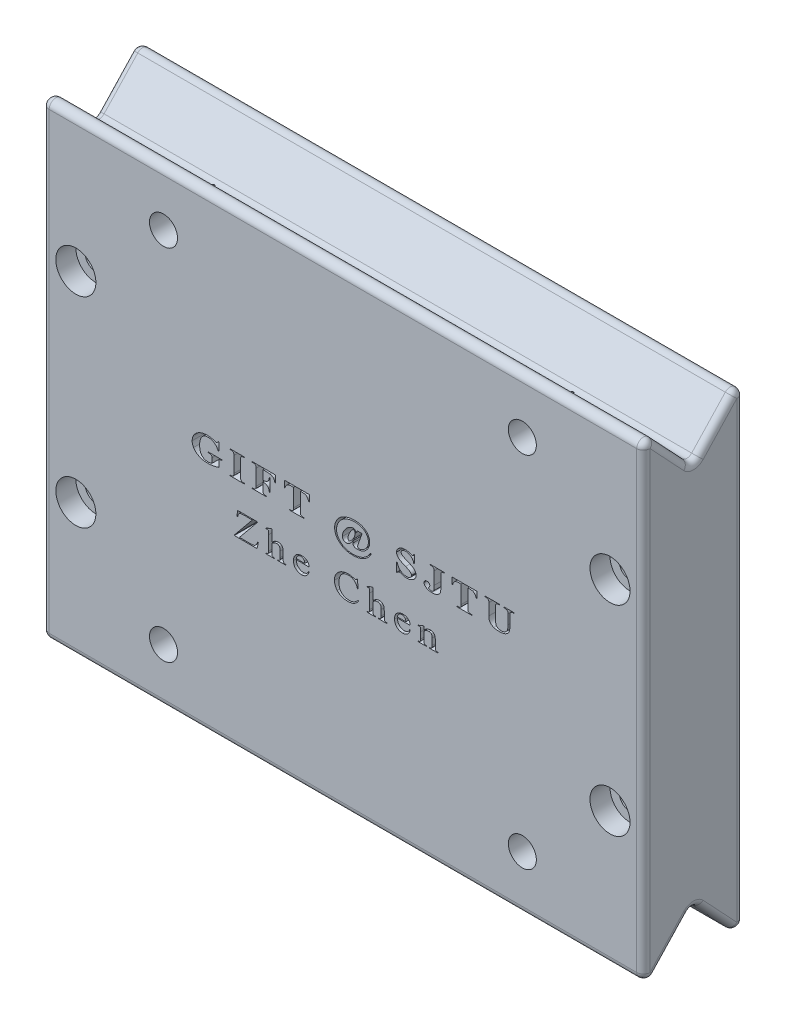
SolidWorks part; units mm, degrees
ref_plane "前视基准面" through (0, 0, 0) normal (0, 0, 1) x (1, 0, 0)
ref_plane "上视基准面" through (0, 0, 0) normal (0, 1, 0) x (1, 0, 0)
ref_plane "右视基准面" through (0, 0, 0) normal (1, 0, 0) x (0, 0, -1)
other "Configuration Table"
sketch "草图1" plane through (0, 0, 0) normal (0, 0, 1) x (1, 0, 0)
  line L0 (0, 0) -> (0, 22500.8852) construction
  line L1 (0, 0) -> (22500.8852, 0) construction
  line L3 (-45, 36.5) -> (45, 36.5)
  line L4 (-45, 36.5) -> (-45, -36.5)
  line L5 (-45, -36.5) -> (45, -36.5)
  line L6 (45, 36.5) -> (45, -36.5)
  line L7 (-45, 36.5) -> (45, -36.5) construction
  line L8 (-45, -36.5) -> (45, 36.5) construction
  circle A0 centre (-26.87, 26.87) radius 2.1
  circle A1 centre (26.87, 26.87) radius 2.1
  circle A2 centre (26.87, -26.87) radius 2.1
  circle A3 centre (-26.87, -26.87) radius 2.1
  point P5 (0, 0)
  dimension "D3" = 53.74
  dimension "D4" = 53.74
  dimension "D5" = 4.2
  dimension "D1" = 90
  dimension "D2" = 73
extrude "凸台-拉伸1" add sketch "草图1" along normal blind 15
sketch "草图2" plane through (0, 0, 0) normal (0, 0, -1) x (-1, 0, 0)
  line L0 (0, 36.5) -> (0, -36.5) construction
  line L1 (45, 36.5) -> (-45, 36.5) construction
  line L2 (45, -36.5) -> (-45, -36.5) construction
  line L3 (-45, 0) -> (45, 0) construction
  line L4 (-45, 36.5) -> (-45, -36.5) construction
  line L5 (45, 36.5) -> (45, -36.5) construction
  circle A0 centre (-26.87, 26.87) radius 4.5
  circle A1 centre (26.87, 26.87) radius 4.5
  circle A2 centre (26.87, -26.87) radius 4.5
  circle A3 centre (-26.87, -26.87) radius 4.5
  dimension "D1" = 9
extrude "切除-拉伸1" cut sketch "草图2" against normal blind 3
sketch "草图5" plane through (-45, 0, 0) normal (-1, 0, 0) x (0, 0, 1)
  line L0 (0, 0) -> (15, 0) construction
  line L1 (15, 36.5) -> (15, -36.5) construction
  line L2 (7.5, 36.5) -> (7.5, -36.5) construction
  line L3 (15, 36.5) -> (0, 36.5) construction
  line L4 (15, -36.5) -> (0, -36.5) construction
  line L5 (0, 36.5) -> (7.5, 28.5)
  line L7 (15, 36.5) -> (0, 36.5)
  line L8 (0, -36.5) -> (7.5, -28.5)
  line L9 (7.5, -28.5) -> (15, -36.5)
  line L10 (15, -36.5) -> (0, -36.5)
  line L11 (7.5, 28.5) -> (15, 36.5)
  dimension "D1" = 8
  dimension "D2" = 8
extrude "切除-拉伸4" cut sketch "草图5" against normal through all
sketch "草图6" plane through (0, 0, 15) normal (0, 0, 1) x (1, 0, 0)
  line L0 (0, 0) -> (-50000, 0) construction
  line L1 (0, 0) -> (0, 50000) construction
  line L2 (-45, 36.5) -> (-45, -36.5) construction
  circle A0 centre (-40, 15) radius 1.6
  circle A1 centre (-40, -15) radius 1.6
  circle A2 centre (40, -15) radius 1.6
  circle A3 centre (40, 15) radius 1.6
  dimension "D1" = 15
  dimension "D2" = 5
  dimension "D3" = 3.2
extrude "切除-拉伸5" cut sketch "草图6" against normal through all
sketch "草图7" plane through (0, 0, 15) normal (0, 0, 1) x (1, 0, 0)
  line L0 (0, 36.5) -> (0, -36.5) construction
  line L1 (45, 36.5) -> (-45, 36.5) construction
  line L2 (-45, -36.5) -> (45, -36.5) construction
  line L3 (-45, 0) -> (45, 0) construction
  line L4 (-45, 36.5) -> (-45, -36.5) construction
  line L5 (45, -36.5) -> (45, 36.5) construction
  circle A0 centre (-40, 15) radius 3
  circle A1 centre (-40, -15) radius 3
  circle A2 centre (40, -15) radius 3
  circle A3 centre (40, 15) radius 3
  dimension "D1" = 6
extrude "切除-拉伸6" cut sketch "草图7" against normal blind 3
fillet "圆角5" radius 1 4 edges at (0, -36.5, 0) (0, -36.5, 15) (-36.597, -28.5, 7.5) (36.597, -28.5, 7.5)
fillet "圆角6" radius 1 4 edges at (0, 36.5, 0) (-36.597, 28.5, 7.5) (36.597, 28.5, 7.5) (0, 36.5, 15)
fillet "圆角7" radius 1 12 edges at (45, 34.9011, 0.6323) (45, -34.9011, 0.6323) (45, -28.9621, 7.5) (45, -34.9011, 14.3677) (45, 34.9011, 14.3677) (45, 28.9621, 7.5) (45, -31.9667, 4.25) (45, -31.9667, 10.75) (45, 0, 0) (45, 0, 15) (45, 31.9667, 10.75) (45, 31.9667, 4.25)
fillet "圆角8" radius 1 12 edges at (-45, 34.9011, 14.3677) (-45, 28.9621, 7.5) (-45, 34.9011, 0.6323) (-45, -34.9011, 0.6323) (-45, -28.9621, 7.5) (-45, -34.9011, 14.3677) (-45, -31.9667, 4.25) (-45, -31.9667, 10.75) (-45, 31.9667, 4.25) (-45, 31.9667, 10.75) (-45, 0, 0) (-45, 0, 15)
sketch "草图11" plane through (0, 0, 15) normal (0, 0, 1) x (1, 0, 0)
  line L0 (-44, 0) -> (44, 0) construction
  line L1 (-44, 33.9712) -> (-44, -33.9712) construction
  line L2 (44, -33.9712) -> (44, 33.9712) construction
  text T0 "<b>GIFT @ SJTU</b>\r\nZhe Chen" font "Times New Roman" height 3.5
extrude "切除-拉伸8" cut sketch "草图11" against normal blind 5
